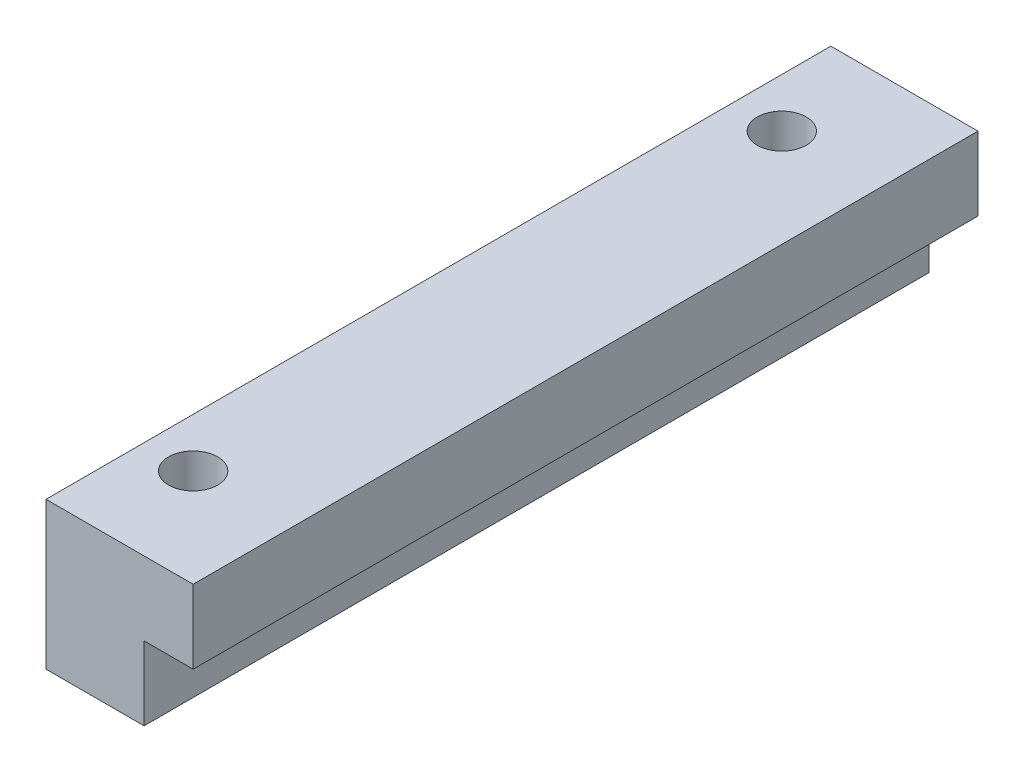
SolidWorks part; units mm, degrees
ref_plane "Front" through (0, 0, 0) normal (0, 0, 1) x (1, 0, 0)
ref_plane "Top" through (0, 0, 0) normal (0, 1, 0) x (1, 0, 0)
ref_plane "Right" through (0, 0, 0) normal (1, 0, 0) x (0, 0, -1)
sketch "Sketch1" plane through (0, 0, 0) normal (0, 1, 0) x (1, 0, 0)
  line L1 (-9.525, -50.8) -> (9.525, -50.8)
  line L2 (-9.525, -50.8) -> (-9.525, 50.8)
  line L3 (-9.525, 50.8) -> (9.525, 50.8)
  line L4 (9.525, -50.8) -> (9.525, 50.8)
  line L5 (-9.525, -50.8) -> (9.525, 50.8) construction
  line L6 (-9.525, 50.8) -> (9.525, -50.8) construction
  point P0 (0, 0)
  dimension "D1" = 101.6
  dimension "D2" = 19.05
extrude "Boss-Extrude1" add sketch "Sketch1" along normal mid plane 19.05 contours L4 L3 L2 L1
sketch "Sketch2" plane through (0, 0, 50.8) normal (0, 0, 1) x (1, 0, 0)
  line L0 (-9.525, 9.525) -> (9.525, 9.525) construction
  line L1 (3.175, 0) -> (9.525, 0)
  line L2 (3.175, 0) -> (3.175, -9.525)
  line L3 (3.175, -9.525) -> (9.525, -9.525)
  line L4 (9.525, 0) -> (9.525, -9.525)
  line L5 (3.175, 0) -> (9.525, -9.525) construction
  line L6 (3.175, -9.525) -> (9.525, 0) construction
  point P0 (6.35, -4.7625)
  dimension "D1" = 6.35
  dimension "D2" = 9.525
extrude "Cut-Extrude1" cut sketch "Sketch2" against normal through all
sketch "Sketch3" plane through (0, 9.525, 0) normal (0, 1, 0) x (1, 0, 0)
  line L0 (-3.175, 38.1) -> (-3.175, -38.1) construction
  line L1 (-50, 0) -> (50, 0) construction
  line L2 (-9.525, -50.8) -> (-9.525, 50.8) construction
  point P0 (-3.175, 38.1)
  point P1 (-3.175, -38.1)
  point P4 (-3.175, 0)
  dimension "D1" = 76.2
  dimension "D2" = 6.35
hole_wizard "1/4 (0.25) Diameter Hole1" positions "Sketch4" profile "Sketch6" hole size "1/4" standard "ANSI Inch"
sketch "Sketch4" plane through (0, 9.525, 0) normal (0, 1, 0) x (1, 0, 0)
  point P0 (-3.175, 38.1)
  point P3 (-3.175, -38.1)
sketch "Sketch6" plane through (-3.175, 9.525, -38.1) normal (1, 0, 0) x (0, 0, 1)
  line L0 (0, 0) -> (0, 27.3077)
  line L1 (0, 27.3077) -> (3.175, 25.4)
  line L2 (3.175, 25.4) -> (3.175, 0)
  line L5 (3.175, 0) -> (0, 0)
  line L10 (0, 27.3077) -> (-3.175, 25.4) construction
  line L11 (0, -6.35) -> (0, 107.95) construction
  dimension "Hole Dia." = 6.35
  dimension "Hole Depth" = 25.4
  dimension "Drill Angle" = 118
